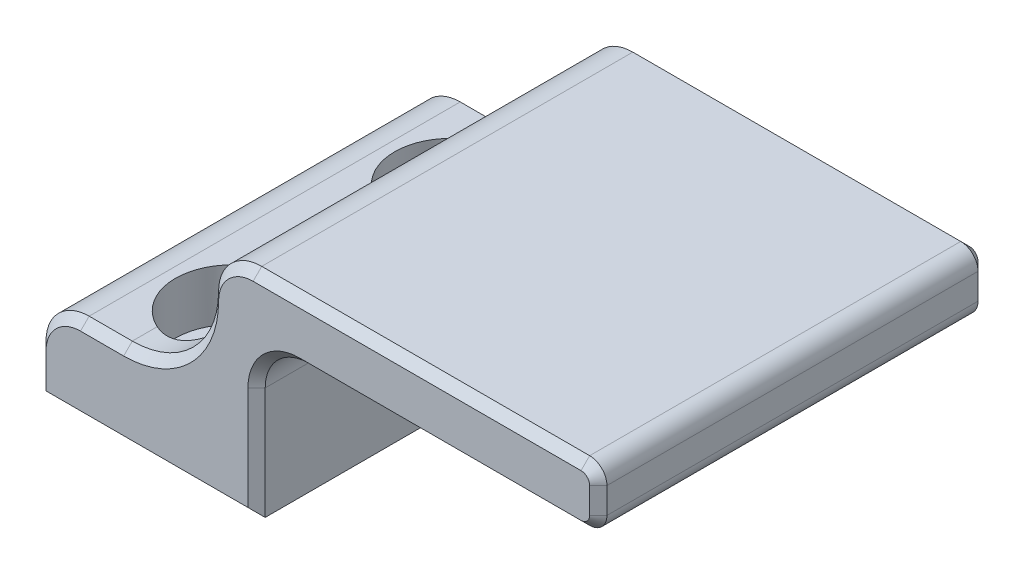
SolidWorks part; units mm, degrees
ref_plane "Front Plane" through (0, 0, 0) normal (0, 0, 1) x (1, 0, 0)
ref_plane "Top Plane" through (0, 0, 0) normal (0, 1, 0) x (1, 0, 0)
ref_plane "Right Plane" through (0, 0, 0) normal (1, 0, 0) x (0, 0, -1)
sketch "Sketch1" plane through (0, 0, 0) normal (0, 0, 1) x (1, 0, 0)
  line L0 (-22.7, -12.5) -> (2.7, -12.5)
  line L5 (2.7, -12.5) -> (2.7, 5.5)
  line L6 (2.7, 5.5) -> (42.3, 5.5)
  line L7 (42.3, 5.5) -> (42.3, 12.5)
  line L8 (42.3, 12.5) -> (-2.7, 12.5)
  line L9 (-2.7, 12.5) -> (-2.7, -2.5)
  line L10 (-2.7, -2.5) -> (-22.7, -2.5)
  line L11 (-22.7, -2.5) -> (-22.7, -12.5)
  line L12 (0, 12.5) -> (0, -12.5) construction
  line L13 (-2.7, 0) -> (2.7, 0) construction
  point P13 (0, 0)
  point P22 (0, 0)
  dimension "D1" = 18
  dimension "D2" = 45
  dimension "D3" = 25.4
  dimension "D4" = 20
  dimension "D5" = 10
  dimension "D6" = 7
extrude "Boss-Extrude1" add sketch "Sketch1" along normal mid plane 45
sketch "Sketch3" plane through (0, -2.5, 0) normal (0, 1, 0) x (1, 0, 0)
  line L2 (-22.7, -22.5) -> (2.7, -22.5) construction
  line L3 (-22.7, -22.5) -> (2.7, -22.5) construction
  circle A0 centre (-10, -12.7) radius 6.5
  circle A1 centre (-10, -12.7) radius 2.921
  point P3 (-10, -22.5)
  dimension "D1" = 13
  dimension "D2" = 5.842
  dimension "D3" = 12.7
extrude "Cut-Extrude1" cut sketch "Sketch3" against normal through all contours A1
extrude "Cut-Extrude2" cut sketch "Sketch3<4>" against normal blind 6
sketch "Sketch3<4>" plane through (0, -2.5, 0) normal (0, 1, 0) x (1, 0, 0) same geometry as "Sketch3"
mirror "Mirror1" about plane through (0, 0, 0) normal (0, 0, 1) of "Cut-Extrude2", "Cut-Extrude1"
sketch "Sketch9" plane through (0, 12.5, 0) normal (0, 1, 0) x (1, 0, 0)
  line L0 (25.9078, 11.1) -> (36.2078, -11.1) construction
  line L1 (42.3, -22.5) -> (42.3, 22.5) construction
  circle A0 centre (25.9078, 11.1) radius 1.0922
  circle A1 centre (36.2078, -11.1) radius 1.0922
  point P4 (31.0578, 0)
  dimension "D3" = 2.1844
  dimension "D1" = 22.2
  dimension "D2" = 10.3
  dimension "D4" = 5
extrude "Cut-Extrude3" [suppressed] cut sketch "Sketch9" against normal through all
fillet "Fillet1" radius 10 1 edges at (-2.7, -2.5, 0)
fillet "Fillet2" radius 5 3 edges at (2.7, 5.5, 0) (-22.7, -2.5, 0) (-2.7, 12.5, 0)
fillet "Fillet4" radius 2 2 edges at (42.3, 12.5, 0) (42.3, 5.5, 0)
chamfer "Chamfer1" distance 1 angle 45 26 edges at (42.3, 9, 22.5) (24, 5.5, 22.5) (4.1645, 4.0355, 22.5) (2.7, -6, 22.5) (-10, -12.5, 22.5) (-22.7, -10, 22.5) (-15.2, -2.5, 22.5) (-5.6289, 0.4289, 22.5) (21.3, 12.5, 22.5) (-15.2, -2.5, -22.5) (-22.7, -10, -22.5) (-10, -12.5, -22.5) (2.7, -6, -22.5) (4.1645, 4.0355, -22.5) (24, 5.5, -22.5) (42.3, 9, -22.5) (21.3, 12.5, -22.5) (-5.6289, 0.4289, -22.5) (41.7142, 6.0858, 22.5) (-21.2355, -3.9645, 22.5) (41.7142, 11.9142, 22.5) (-21.2355, -3.9645, -22.5) (41.7142, 6.0858, -22.5) (41.7142, 11.9142, -22.5) (-1.2355, 11.0355, 22.5) (-1.2355, 11.0355, -22.5)
